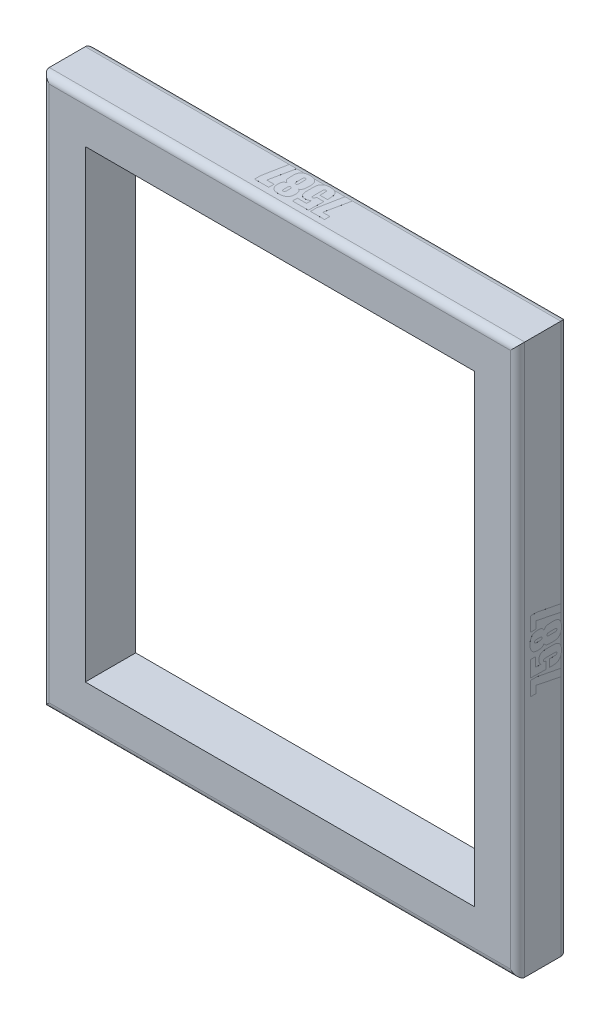
SolidWorks part; units mm, degrees
ref_plane "Front Plane" through (0, 0, 0) normal (0, 0, 1) x (1, 0, 0)
ref_plane "Top Plane" through (0, 0, 0) normal (0, 1, 0) x (1, 0, 0)
ref_plane "Right Plane" through (0, 0, 0) normal (1, 0, 0) x (0, 0, -1)
sketch "Sketch1" plane through (0, 0, 0) normal (0, 0, 1) x (1, 0, 0)
  line L1 (-50.8, 0) -> (-736.6, 0)
  line L2 (-50.8, 0) -> (-50.8, 817.499)
  line L3 (-50.8, 817.499) -> (-736.6, 817.499)
  line L4 (-736.6, 0) -> (-736.6, 817.499)
  line L5 (25.4, -76.2) -> (-812.8, -76.2)
  line L6 (25.4, -76.2) -> (25.4, 893.699)
  line L7 (25.4, 893.699) -> (-812.8, 893.699)
  line L8 (-812.8, -76.2) -> (-812.8, 893.699)
  dimension "D1" = 76.2
  dimension "D2" = 76.2
  dimension "D3" = 76.2
  dimension "D4" = 76.2
extrude "Boss-Extrude1" add sketch "Sketch1" against normal blind 88.9
fillet "Fillet1" radius 12.7 8 edges at (-812.8, 408.7495, -88.9) (-393.7, 893.699, -88.9) (-393.7, -76.2, -88.9) (25.4, 408.7495, -88.9) (25.4, 408.7495, 0) (-393.7, 893.699, 0) (-393.7, -76.2, 0) (-812.8, 408.7495, 0)
sketch "Sketch6" plane through (0, -76.2, 0) normal (0, -1, 0) x (1, 0, 0)
  text T0 " 7587" font "Impact" height in points 190
extrude "Boss-Extrude4" add sketch "Sketch6" along normal blind 0.0254
sketch "Sketch9" plane through (0, 893.699, 0) normal (0, 1, 0) x (1, 0, 0)
  text T0 " 7587" font "Impact" height in points 190
extrude "Boss-Extrude6" add sketch "Sketch9" along normal blind 0.0254
sketch "Sketch10" plane through (25.4, 0, 0) normal (1, 0, 0) x (0, 0, -1)
  text T0 "7587" font "Impact" height in points 190
extrude "Boss-Extrude7" add sketch "Sketch10" along normal blind 0.0254
sketch "Sketch11" plane through (-812.8, 0, 0) normal (-1, 0, 0) x (0, 0, 1)
  text T0 "7587" font "Impact" height in points 190
extrude "Boss-Extrude8" add sketch "Sketch11" along normal blind 0.0254
